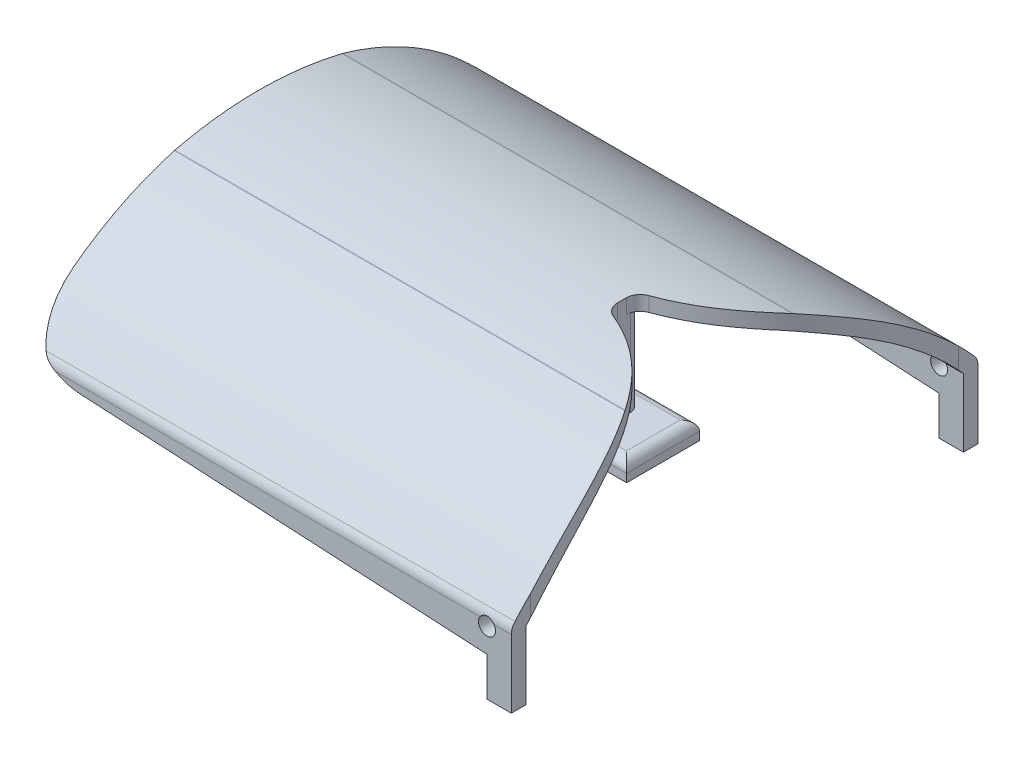
SolidWorks part; units mm, degrees
ref_plane "Front Plane" through (0, 0, 0) normal (0, 0, 1) x (1, 0, 0)
ref_plane "Top Plane" through (0, 0, 0) normal (0, 1, 0) x (1, 0, 0)
ref_plane "Right Plane" through (0, 0, 0) normal (1, 0, 0) x (0, 0, -1)
sketch "Sketch1" plane through (0, 0, 0) normal (1, 0, 0) x (0, 0, -1)
  line L1 (-45, -18) -> (-45, -32)
  line L2 (45, -18) -> (45, -32)
  arc A0 (-16.5013, 0) -> (-45, -18) centre (0, -57.6863) ccw
  arc A1 (16.5013, 0) -> (45, -18) centre (0, -57.6863) cw
  arc A2 (-16.5013, 0) -> (16.5013, 0) centre (0, -68.0272) cw
  dimension "D4" = 60
  dimension "D5" = 60
  dimension "D3" = 70
  dimension "D1" = 90
  dimension "D2" = 14
  dimension "D6" = 33.0027
  dimension "D7" = 28.4987
extrude "Extrude-Thin1" add sketch "Sketch1" along normal blind 100 thin thin type one direction wall 3
sketch "Sketch5" plane through (0, 0, 0) normal (0, 1, 0) x (1, 0, 0)
  line L0 (100, 17.2677) -> (100, 48) construction
  line L2 (74.7808, 3) -> (74.7808, -3)
  line L3 (-20.335, 0) -> (20.335, 0) construction
  line L4 (100, 44) -> (100, -44)
  spline S0 degree 2 poles (74.7808, 3) (97.6341, 10.563) (100, 44) knots 0 0 0 1 1 1
  spline S1 degree 2 poles (74.7808, -3) (97.6341, -10.563) (100, -44) knots 0 0 0 1 1 1
  point P4 (74.7808, 0)
  point P5 (0, 0)
  point P7 (0, 0)
  point P8 (0, 0)
  point P9 (0, 0)
  dimension "D1" = 3
extrude "Cut-Extrude2" cut sketch "Sketch5" against normal mid plane 67
fillet "Fillet1" radius 3 6 edges at (50, -16.8819, -48) (50, -16.8819, 48) (74.7808, 3.4098, 3) (74.7808, 3.4098, -3) (46.3282, 2.9011, -17.2677) (46.3282, 2.9011, 17.2677)
sketch "Sketch6" plane through (0, 0, -48) normal (0, 0, -1) x (-1, 0, 0)
  line L1 (-95, -24) -> (13.6709, -24)
  line L2 (-95, -24) -> (-95, -41.8798)
  line L3 (-95, -41.8798) -> (13.6709, -41.8798)
  line L4 (13.6709, -24) -> (13.6709, -41.8798)
  line L6 (-100, -32) -> (0, -32) construction
  line L7 (-100, -32) -> (-100, -18) construction
  dimension "D1" = 5
  dimension "D3" = 8
extrude "Cut-Extrude3" cut sketch "Sketch6" against normal blind 166
sketch "Sketch8" plane through (0, 0, 0) normal (0, 0, 1) x (1, 0, 0)
  line L0 (0, 1.9728) -> (-2.8489, -18)
  line L1 (100, -18) -> (0, -18) construction
  line L2 (-2.8489, -18) -> (7.1511, -18)
  line L3 (7.1511, -18) -> (15, 1.9728)
  line L4 (0, -18) -> (0, -24) construction
  line L5 (15, 1.9728) -> (0, 1.9728)
  point P3 (0, 0)
  point P5 (0, 0)
  point P6 (0, 0)
  point P7 (-2.8682, -18.1221)
  point P8 (15, 1.9728)
  point P9 (6.9177, -18)
  point P14 (0, 0)
  dimension "D1" = 10
  dimension "D2" = 15
  dimension "D3" = 2.8489
extrude "Boss-Extrude1" add sketch "Sketch8" along normal mid plane 21 contours L3 L5 L0 L2
sketch "Sketch10" plane through (0, 0, 10.5) normal (0, 0, 1) x (1, 0, 0)
  line L0 (-2.8489, -18) -> (7.1511, -18) construction
  line L2 (-0.3489, -18) -> (3.9872, -18)
  arc A0 (-0.3489, -18) -> (3.9872, -18) centre (1.8191, -16.7552) cw
  point P3 (2.1437, -17.8084)
  point P6 (0, 0)
  dimension "D1" = 2.5
  dimension "D2" = 2.5
extrude "Cut-Extrude4" cut sketch "Sketch10" against normal blind 27 contours A0 L2
sketch "Sketch11" plane through (0, 0, -48) normal (0, 0, -1) x (-1, 0, 0)
  line L1 (0, -24) -> (-95, -24) construction
  line L2 (-100, -32) -> (-100, -18) construction
  circle A0 centre (-95, -19) radius 1.75
  point P2 (-95.1265, -20.9768)
  dimension "D1" = 3.5
  dimension "D2" = 5
  dimension "D3" = 5
extrude "Cut-Extrude5" cut sketch "Sketch11" against normal blind 5
mirror "Mirror1" about plane through (0, 0, 0) normal (0, 0, 1) of "Cut-Extrude5"
sketch "Sketch12" plane through (0, 0, 0) normal (0, 0, 1) x (1, 0, 0)
  line L0 (74.7808, 1.9728) -> (74.7808, -15.9018)
  line L1 (74.7808, -15.9018) -> (83.2199, -15.9018)
  line L2 (83.2199, -15.9018) -> (83.2199, -19.5891)
  line L3 (83.2199, -19.5891) -> (67.6774, -19.5891)
  line L4 (67.6774, -19.5891) -> (67.6774, 1.9728)
  line L5 (74.7808, 1.9728) -> (15, 1.9728) construction
  line L6 (67.6774, 1.9728) -> (74.7808, 1.9728)
extrude "Boss-Extrude2" add sketch "Sketch12" along normal mid plane 15
sketch "Sketch13" plane through (74.7808, 0, 0) normal (1, 0, 0) x (0, 0, -1)
  line L0 (-7.5, -15.9018) -> (-7.5, 1.5698) construction
  line L2 (-7.5, 1.5698) -> (-7.5, -15.9018)
  line L3 (-7.5, -15.9018) -> (-3.705, -15.9018)
  line L4 (-3.705, 1.8746) -> (-3.705, -15.9018)
  line L5 (0, 20.5226) -> (0, -20.5226) construction
  line L6 (7.5, -15.9018) -> (3.705, -15.9018)
  line L7 (3.705, 1.8746) -> (3.705, -15.9018)
  line L9 (7.5, 1.5698) -> (7.5, -15.9018)
  line L10 (-7.5, -15.9018) -> (7.5, -15.9018) construction
  arc A0 (-0.8964, 1.967) -> (-7.5, 1.5698) centre (0, -68.0272) ccw construction
  arc A1 (-7.5, 1.5698) -> (-3.705, 1.8746) centre (0, -68.0272) cw
  arc A2 (3.705, 1.8746) -> (7.5, 1.5698) centre (0, -68.0272) cw
extrude "Cut-Extrude6" cut sketch "Sketch13" against normal blind 15
fillet "Fillet3" radius 2 7 edges at (67.6774, -7.0136, -3.705) (67.6774, -7.0136, 3.705) (74.7808, -7.0136, -3.705) (74.7808, -7.0136, 3.705) (75.4486, -15.9018, 7.5) (83.2199, -15.9018, 0) (75.4486, -15.9018, -7.5)
sketch "Sketch15" plane through (0, 0, -48) normal (0, 0, -1) x (-1, 0, 0)
  line L0 (-95, -24) -> (0, -18.8601)
  line L1 (0, 20.5226) -> (0, -20.5226) construction
  line L2 (0, -18.8601) -> (0, -26.572)
  line L3 (0, -26.572) -> (-95, -24)
extrude "Cut-Extrude7" cut sketch "Sketch15" against normal blind 5
mirror "Mirror2" about plane through (0, 0, 0) normal (0, 0, 1) of "Cut-Extrude7"
fillet "Fillet5" radius 12 2 edges at (0, -18.8601, 46.5) (0, -18.8601, -46.5)
